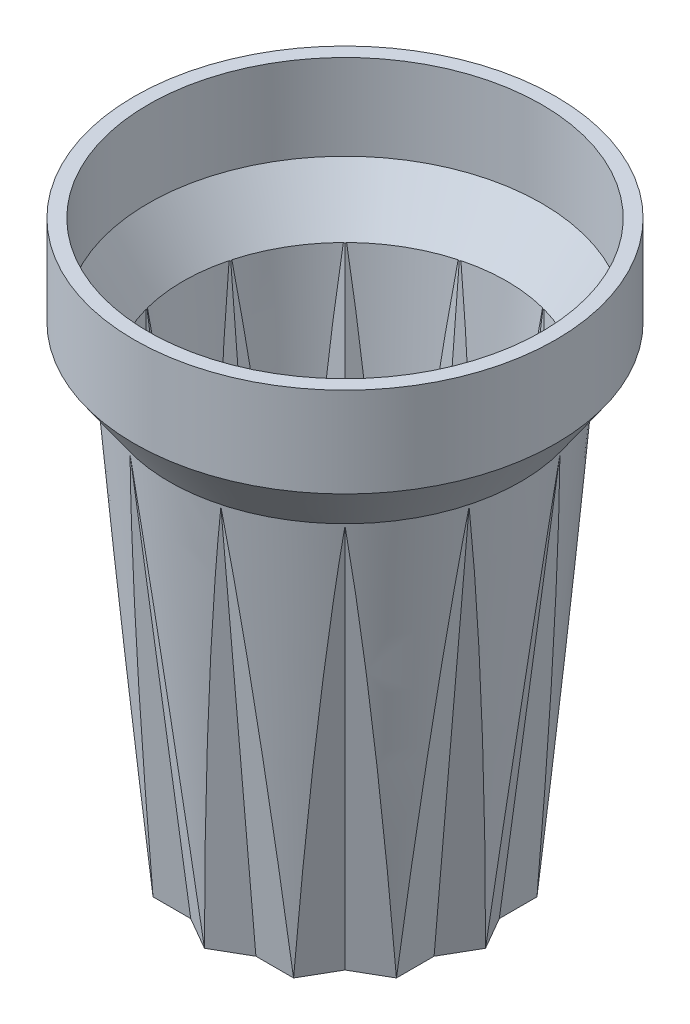
SolidWorks part; units mm, degrees
ref_plane "Plano frontal" through (0, 0, 0) normal (0, 0, 1) x (1, 0, 0)
ref_plane "Plano superior" through (0, 0, 0) normal (0, 1, 0) x (1, 0, 0)
ref_plane "Plano direito" through (0, 0, 0) normal (1, 0, 0) x (0, 0, -1)
sketch "Esboço4" plane through (0, 0, 0) normal (0, 0, 1) x (1, 0, 0)
  line L0 (-10, 0) -> (-12.5, 30)
  line L1 (-12.5, 30) -> (-15, 33.6019)
  line L2 (-15, 33.6019) -> (-15, 40)
  line L3 (-10, 0) -> (0, 0)
  line L4 (0, 0) -> (0, 40) construction
  line L5 (-15, 40) -> (0, 40)
  line L6 (0, 0) -> (0, 40)
  dimension "D5" = 40
  dimension "D1" = 20
  dimension "D2" = 25
  dimension "D3" = 30
  dimension "D4" = 30
  dimension "D6" = 30
revolve "Revolução1" add sketch "Esboço4" angle 360 about L4
sketch "Esboço5" plane through (0, 0, 0) normal (0, -1, 0) x (1, 0, 0)
  line L0 (0, 0) -> (5, 8.6603) construction
  line L1 (0, 10) -> (-2.3205, 8.6603)
  line L2 (-8.6603, 5) -> (-8.6603, 2.3205)
  line L3 (-8.6603, -5) -> (-6.3397, -6.3397)
  line L4 (0, -10) -> (2.3205, -8.6603)
  line L5 (8.6603, -5) -> (8.6603, -2.3205)
  line L6 (8.6603, 5) -> (6.3397, 6.3397)
  line L7 (5, 8.6603) -> (2.3205, 8.6603)
  line L8 (-5, 8.6603) -> (-6.3397, 6.3397)
  line L9 (-10, 0) -> (-8.6603, -2.3205)
  line L10 (-5, -8.6603) -> (-2.3205, -8.6603)
  line L11 (5, -8.6603) -> (6.3397, -6.3397)
  line L12 (10, 0) -> (8.6603, 2.3205)
  line L13 (0, 0) -> (0, 10) construction
  line L14 (-8.6603, 2.3205) -> (-10, 0)
  line L15 (-6.3397, 6.3397) -> (-8.6603, 5)
  line L16 (-2.3205, 8.6603) -> (-5, 8.6603)
  line L17 (2.3205, 8.6603) -> (0, 10)
  line L18 (6.3397, 6.3397) -> (5, 8.6603)
  line L19 (8.6603, 2.3205) -> (8.6603, 5)
  line L20 (8.6603, -2.3205) -> (10, 0)
  line L21 (6.3397, -6.3397) -> (8.6603, -5)
  line L22 (2.3205, -8.6603) -> (5, -8.6603)
  line L23 (-2.3205, -8.6603) -> (0, -10)
  line L24 (-6.3397, -6.3397) -> (-5, -8.6603)
  line L25 (-8.6603, -2.3205) -> (-8.6603, -5)
  circle A0 centre (0, 0) radius 8.6603 construction
  circle A1 centre (0, 0) radius 8.6603 construction
extrude "Corte-extrusão1" cut sketch "Esboço5" against normal blind 30 draft 6.5 flip side to cut
shell "Casca1" thickness 1 removed face at (0, 40, -15)
scale "Escala2" scale about origin uniform scaling yes scale factor 2.5
